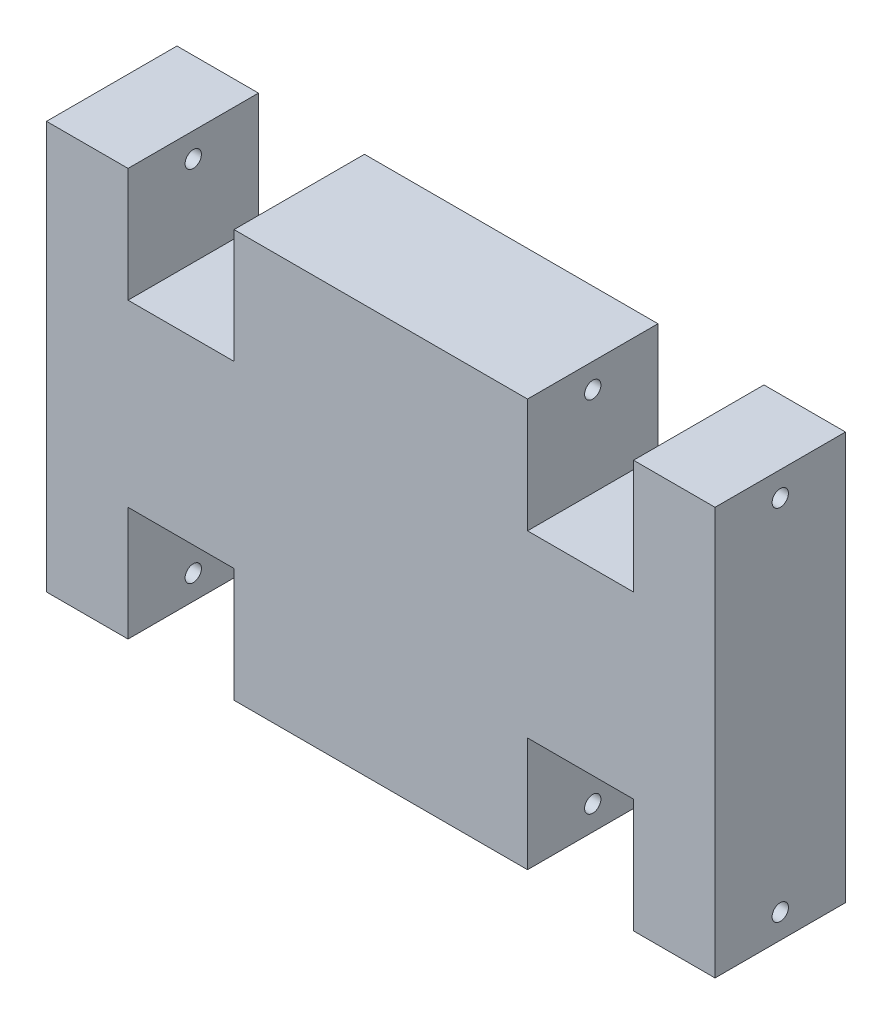
SolidWorks part; units mm, degrees
ref_plane "Alzado" through (0, 0, 0) normal (0, 0, 1) x (1, 0, 0)
ref_plane "Planta" through (0, 0, 0) normal (0, 1, 0) x (1, 0, 0)
ref_plane "Vista lateral" through (0, 0, 0) normal (1, 0, 0) x (0, 0, -1)
sketch "Croquis1" plane through (0, 0, 0) normal (0, 0, 1) x (1, 0, 0)
  line L0 (0, 0) -> (5, 0)
  line L1 (5, 0) -> (5, 7)
  line L2 (5, 7) -> (11.5, 7)
  line L3 (11.5, 7) -> (11.5, 0)
  line L4 (11.5, 0) -> (29.5, 0)
  line L5 (29.5, 7) -> (36, 7)
  line L6 (36, 7) -> (36, 0)
  line L7 (36, 0) -> (41, 0)
  line L8 (29.5, 7) -> (29.5, 0)
  line L10 (29.5, 18) -> (29.5, 25)
  line L11 (36, 25) -> (41, 25)
  line L12 (36, 18) -> (36, 25)
  line L13 (29.5, 18) -> (36, 18)
  line L14 (11.5, 25) -> (29.5, 25)
  line L15 (11.5, 18) -> (11.5, 25)
  line L16 (5, 18) -> (11.5, 18)
  line L17 (5, 25) -> (5, 18)
  line L18 (0, 25) -> (5, 25)
  line L19 (0, 25) -> (0, 0)
  line L20 (41, 25) -> (41, 0)
  dimension "D1" = 6.5
  dimension "D2" = 5
  dimension "D3" = 18
  dimension "D4" = 6.5
  dimension "D5" = 5
  dimension "D6" = 25
  dimension "D7" = 7
  dimension "D8" = 7
  dimension "D9" = 25
  dimension "D10" = 7
  dimension "D11" = 25
extrude "Saliente-Extruir2" add sketch "Croquis1" along normal blind 8
sketch "Croquis3" plane through (41, 0, 0) normal (1, 0, 0) x (0, 0, -1)
  circle A0 centre (-4, 23.4982) radius 0.5
  circle A1 centre (-4, 1.5018) radius 0.5
  point P0 (0, 0)
  dimension "D1" = 1
extrude "Cortar-Extruir1" cut sketch "Croquis3" against normal blind 45 contours A1 | A0
